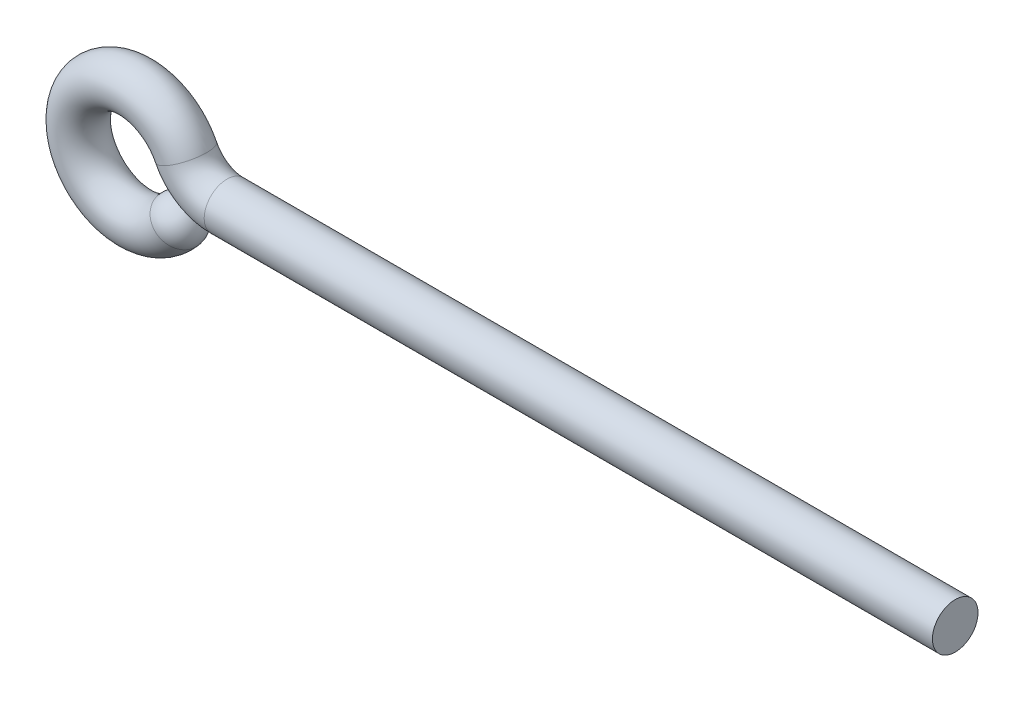
SolidWorks part; units mm, degrees
ref_plane "Front Plane" through (0, 0, 0) normal (0, 0, 1) x (1, 0, 0)
ref_plane "Top Plane" through (0, 0, 0) normal (0, 1, 0) x (1, 0, 0)
ref_plane "Right Plane" through (0, 0, 0) normal (1, 0, 0) x (0, 0, -1)
sketch "Sketch1" plane through (0, 0, 0) normal (0, 0, 1) x (1, 0, 0)
  line L0 (0, 0) -> (-30, 0) construction
  line L1 (-30, 0) -> (-20.4244, -8.0348) construction
  line L2 (-9.8444, 0) -> (0, 0)
  arc A0 (-24.3585, -0.4766) -> (-24.3384, 0) centre (-30, 0) ccw
  arc A1 (-18.8024, 5.5556) -> (-20.4244, -8.0348) centre (-30, 0) ccw
  arc A2 (-18.8024, 5.5556) -> (-9.8444, 0) centre (-9.8444, 10) ccw
  point P5 (0, 0)
  point P10 (-17.5, 0)
  dimension "D3" = 12.5
  dimension "D4" = 10
  dimension "D1" = 30
  dimension "D2" = 40
ref_plane "Plane1" through (0, 0, 0) normal (1, 0, 0) x (0, 0, -1)
sketch "Sketch2" plane through (0, 0, 0) normal (1, 0, 0) x (0, 0, -1)
  circle A0 centre (0, 0) radius 5
  dimension "D1" = 10
sweep "Sweep2" add profiles "Sketch2" path "Sketch1"
dome "Dome3" faces to dome 1 distance 5 reverse direction no elliptical dome no face at (-20.4244, -8.0348, -5) parameters "D1"=5
sketch "Sketch4" plane through (0, 0, 0) normal (1, 0, 0) x (0, 0, -1)
  circle A0 centre (0, 0) radius 5 construction
  circle A1 centre (0, 0) radius 5
extrude "Boss-Extrude2" add sketch "Sketch4" along normal blind 150
